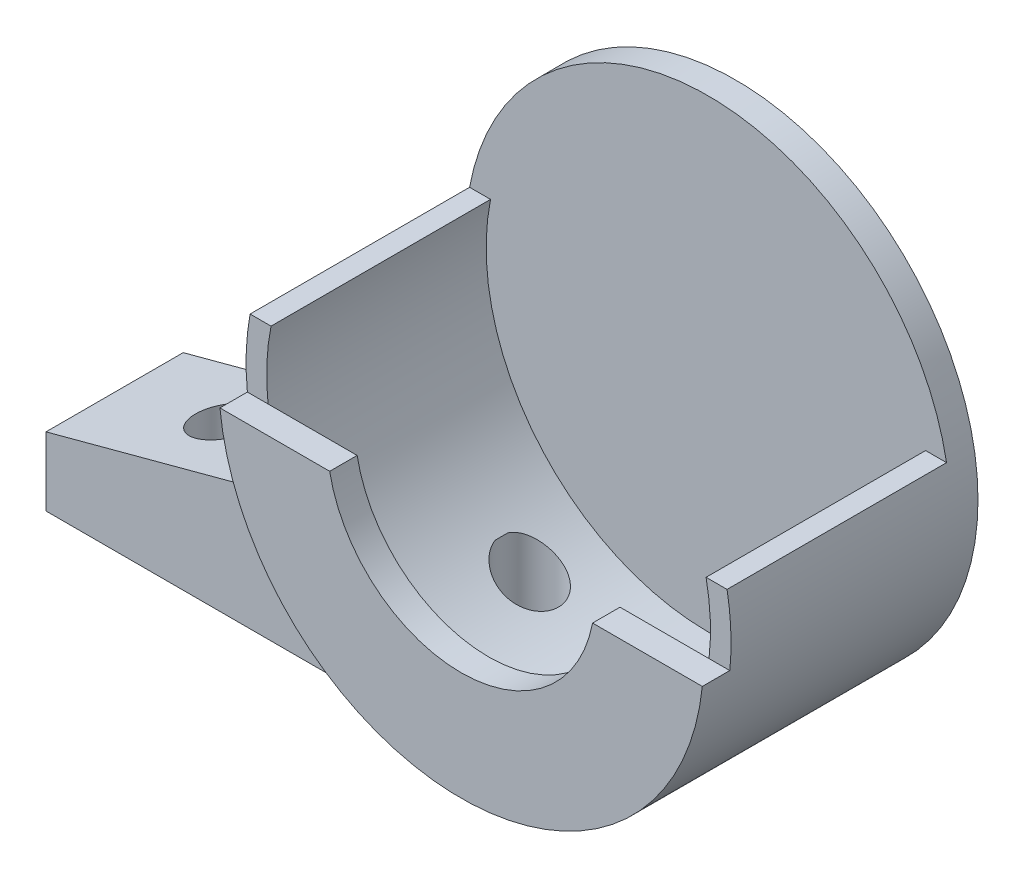
SolidWorks part; units mm, degrees
ref_plane "Front Plane" through (0, 0, 0) normal (0, 0, 1) x (1, 0, 0)
ref_plane "Top Plane" through (0, 0, 0) normal (0, 1, 0) x (1, 0, 0)
ref_plane "Right Plane" through (0, 0, 0) normal (1, 0, 0) x (0, 0, -1)
sketch "Sketch1" plane through (0, 0, 0) normal (0, 0, 1) x (1, 0, 0)
  line L0 (-17.3829, 3.2) -> (-15.8553, 3.2)
  line L1 (15.8553, 3.2) -> (17.3829, 3.2)
  circle A0 centre (0, 0) radius 16.175
  circle A1 centre (0, 0) radius 17.675
  point P8 (0, 0)
  point P9 (0, 0)
  point P10 (16.175, 0)
  dimension "D1" = 32.35
  dimension "D2" = 35.35
  dimension "D3" = 3.2
extrude "Boss-Extrude1" add sketch "Sketch1" against normal blind 2 contours A0 | L0 A1 L1 A0 | L1 A1 L0 A0 region at (0, 17.2984, 0) region at (-16.6191, 2.7895, 0) region at (0, 0, 0)
extrude "Boss-Extrude2" add sketch "Sketch1<4>" along normal blind 16 contours L0 A1 L1 A0 region at (-16.6191, 2.7895, 0)
sketch "Sketch1<4>" plane through (0, 0, 0) normal (0, 0, 1) x (1, 0, 0) same geometry as "Sketch1"
sketch "Sketch2" plane through (0, 0, 16) normal (0, 0, 1) x (1, 0, 0)
  line L0 (-17.5805, -1.825) -> (-9.5805, -1.825)
  line L1 (17.5805, -1.825) -> (9.5805, -1.825)
  circle A0 centre (0, 0) radius 17.675
  arc A1 (9.5805, -1.825) -> (-9.5805, -1.825) centre (0, 0) cw
  point P9 (0, 0)
  arc M4 (-17.3829, 3.2) -> (17.3829, 3.2) centre (0, 0) ccw
  arc M6 (15.8553, 3.2) -> (-15.8553, 3.2) centre (0, 0) cw
  dimension "D1" = 8
  dimension "D2" = 1.825
extrude "Boss-Extrude3" add sketch "Sketch2" along normal blind 2 contours L1 A1 L0 M6 | L1 L0 M4 M6 region at (-16.8261, -2.2107, 16) region at (-12.8261, -2.177, 16)
sketch "Sketch3" plane through (0, 0, 0) normal (0, 0, 1) x (1, 0, 0)
  line L1 (-38.2579, -17.675) -> (-17.3829, 3.2)
  line L2 (-38.2579, -17.675) -> (-38.2579, -22.675)
  line L3 (-38.2579, -22.675) -> (0, -22.675)
  line L4 (0, -22.675) -> (0, -17.675)
  arc A1 (0, -17.675) -> (-17.3829, 3.2) centre (0, 0) cw
  point P2 (-35.3449, -17.6699)
  point P4 (-5.5769, -21.7721)
  dimension "D1" = 5
  dimension "D2" = 135
extrude "Boss-Extrude4" add sketch "Sketch3" along normal blind 10
sketch "Sketch5" plane through (0, -22.675, 0) normal (0, -1, 0) x (1, 0, 0)
  line L5 (-38.2579, 10) -> (-38.2579, 0) construction
  line L6 (0, 10) -> (0, 0) construction
  circle A0 centre (-30.2579, 5) radius 2.1
  circle A1 centre (-8, 5) radius 2.1
  point P3 (-38.2579, 5)
  point P7 (0, 0)
  dimension "D1" = 4.2
  dimension "D2" = 8
  dimension "D3" = 8
extrude "Cut-Extrude3" cut sketch "Sketch5" against normal blind 10 contours A0 | A1 region at (-30.2579, -22.675, 5) region at (-8, -22.675, 5)
ref_axis "Axis1" through (0, 0, 33.509) along (0, 0, -1)
sketch "Sketch6" plane through (0, 0, 10) normal (0, 0, 1) x (1, 0, 0)
  line L0 (-38.2579, -17.675) -> (-22.583, -13.4749)
  line L1 (-22.583, -13.4749) -> (-18.3829, 2.2)
  line L2 (-17.3829, 3.2) -> (-38.2579, -17.675) construction
  line L3 (-38.2579, -17.675) -> (-38.2579, -22.675) construction
  line L4 (0, -22.675) -> (0, -17.675) construction
  line L5 (-17.3829, 3.2) -> (-15.8553, 3.2) construction
  line L6 (-38.2579, -17.675) -> (-18.3829, 2.2)
  dimension "D1" = 105
  dimension "D2" = 15
  dimension "D3" = 1
extrude "Cut-Extrude5" cut sketch "Sketch6" against normal through all both and the other way through all
